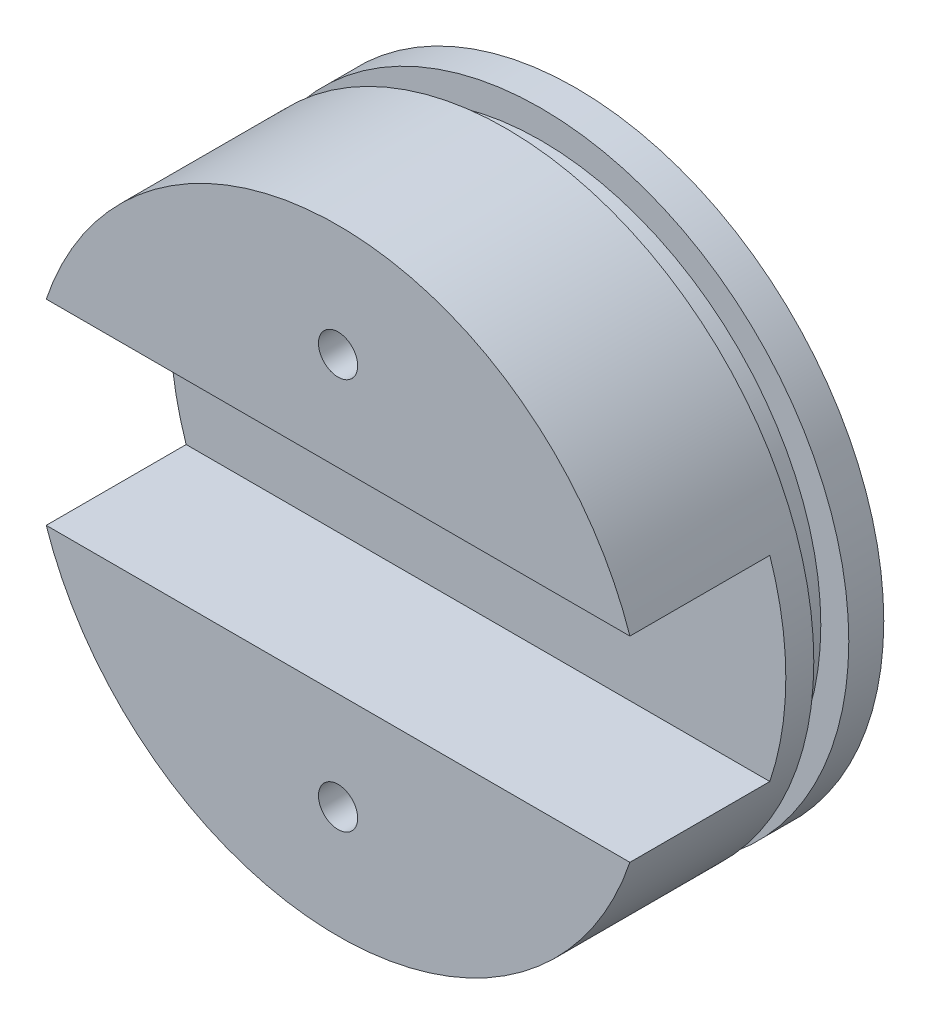
SolidWorks part; units mm, degrees
ref_plane "Front Plane" through (0, 0, 0) normal (0, 0, 1) x (1, 0, 0)
ref_plane "Top Plane" through (0, 0, 0) normal (0, 1, 0) x (1, 0, 0)
ref_plane "Right Plane" through (0, 0, 0) normal (1, 0, 0) x (0, 0, -1)
sketch "Sketch1" plane through (0, 0, 0) normal (0, 0, 1) x (1, 0, 0)
  circle A0 centre (0, 0) radius 22
  dimension "D1" = 44
extrude "Boss-Extrude1" add sketch "Sketch1" along normal blind 2.5
sketch "Sketch2" plane through (0, 0, 0) normal (0, 0, 1) x (1, 0, 0)
  circle A0 centre (0, 0) radius 20
  dimension "D1" = 40
extrude "Boss-Extrude2" add sketch "Sketch2" along normal blind 5
extrude "Boss-Extrude3" add sketch "Sketch1<2>" along normal blind 12 from surface starting at face at (20, 0, 5)
sketch "Sketch1<2>" plane through (0, 0, 0) normal (0, 0, 1) x (1, 0, 0) same geometry as "Sketch1"
sketch "Sketch3" plane through (0, 0, 0) normal (0, 0, 1) x (1, 0, 0)
  line L0 (-29.4379, 7) -> (26.9011, 7)
  line L1 (-29.4379, -7) -> (26.9011, -7)
  line L2 (-29.4379, 7) -> (-29.4379, -7)
  line L3 (26.9011, 7) -> (26.9011, -7)
  dimension "D1" = 7
  dimension "D2" = 7
extrude "Cut-Extrude1" cut sketch "Sketch3" against normal blind 10 from surface starting at face at (22, 0, 17)
sketch "Sketch4" plane through (0, 0, 0) normal (0, 0, 1) x (1, 0, 0)
  line L0 (0, 0) -> (33.385, 0) construction
  circle A0 centre (0, 14) radius 1.4
  circle A1 centre (0, -14) radius 1.4
  dimension "D1" = 2.8
  dimension "D2" = 14
extrude "Cut-Extrude2" cut sketch "Sketch4" along normal through all
sketch "Sketch5" plane through (0, 0, 0) normal (0, 0, 1) x (1, 0, 0)
  line L0 (0, 0) -> (-28.8832, 0) construction
  circle A0 centre (0, 14) radius 3
  circle A1 centre (0, -14) radius 3
  dimension "D1" = 6
extrude "Cut-Extrude3" cut sketch "Sketch5" along normal blind 1.3 from surface starting at face at (1.4, 14, 0)
